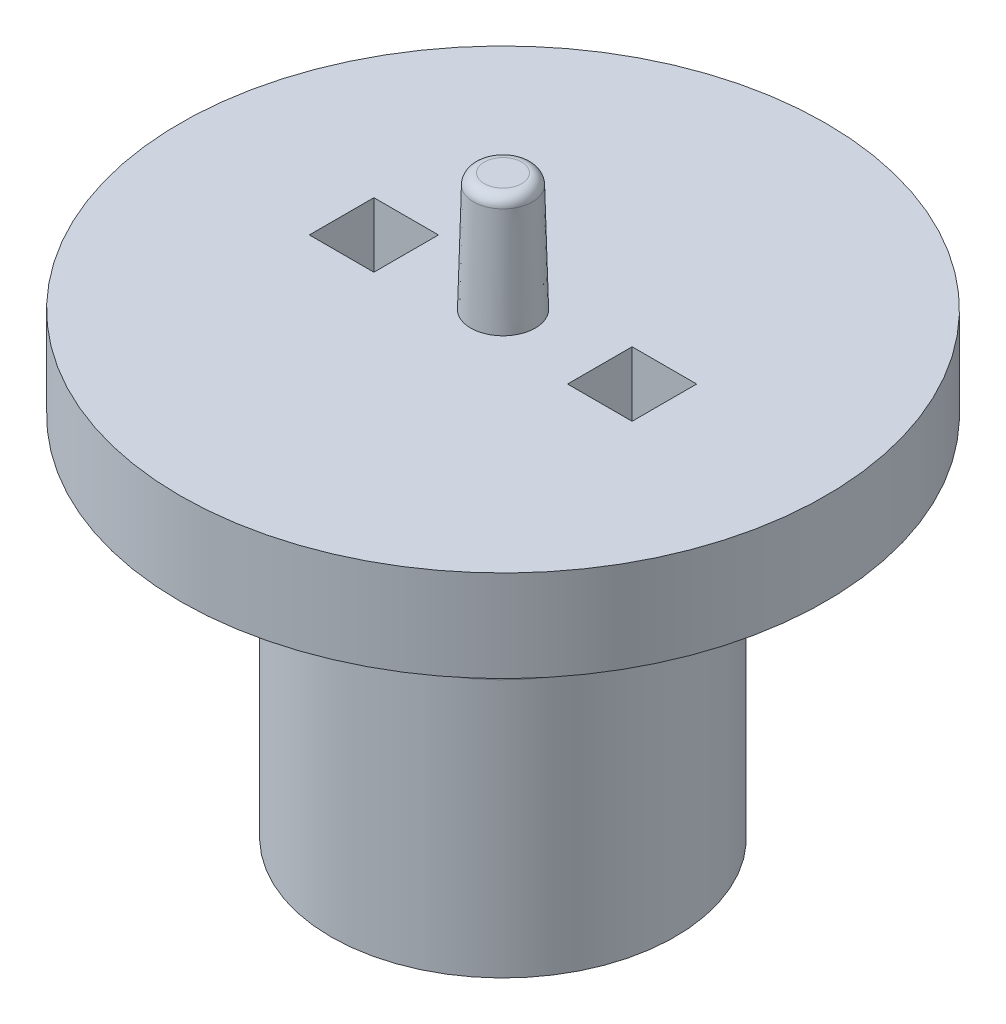
SolidWorks part; units mm, degrees
ref_plane "Front Plane" through (0, 0, 0) normal (0, 0, 1) x (1, 0, 0)
ref_plane "Top Plane" through (0, 0, 0) normal (0, 1, 0) x (1, 0, 0)
ref_plane "Right Plane" through (0, 0, 0) normal (1, 0, 0) x (0, 0, -1)
sketch "Sketch1" plane through (0, 0, 0) normal (0, 1, 0) x (1, 0, 0)
  circle A0 centre (0, 0) radius 8
  circle A1 centre (0, 0) radius 2.575
  dimension "D1" = 16
  dimension "D2" = 5.15
extrude "Boss-Extrude1" add sketch "Sketch1" along normal blind 15
sketch "Sketch2" plane through (0, 0, 0) normal (0, 0, 1) x (1, 0, 0)
  line L1 (0, 7.5) -> (0, 15) construction
  line L2 (0, 7.5) -> (0, 0) construction
  circle A0 centre (0, 7.5) radius 1.25
  dimension "D1" = 2.5
extrude "Cut-Extrude1" cut sketch "Sketch2" against normal through all contours A0
ref_plane "Plane1" through (0, 0, -8) normal (0, 0, -1) x (-1, 0, 0)
sketch "Sketch12" plane through (0, 15, 0) normal (0, 1, 0) x (1, 0, 0)
  circle A0 centre (0, 0) radius 8
  circle A1 centre (0, 0) radius 8 construction
extrude "Boss-Extrude3" add sketch "Sketch12" along normal blind 2
sketch "Sketch10" plane through (0, 17, 0) normal (0, 1, 0) x (1, 0, 0)
  circle A0 centre (0, 0) radius 7.5
sketch "Sketch11" plane through (0, 17, 0) normal (0, 1, 0) x (1, 0, 0)
  line L0 (6, 0) -> (0, 0) construction
  line L1 (-7.5, 1.5) -> (-4.5, 1.5)
  line L2 (-7.5, 1.5) -> (-7.5, -1.5)
  line L3 (-7.5, -1.5) -> (-4.5, -1.5)
  line L4 (-4.5, 1.5) -> (-4.5, -1.5)
  line L5 (-7.5, 1.5) -> (-4.5, -1.5) construction
  line L6 (-7.5, -1.5) -> (-4.5, 1.5) construction
  line L7 (4.5, 1.5) -> (7.5, 1.5)
  line L8 (4.5, 1.5) -> (4.5, -1.5)
  line L9 (4.5, -1.5) -> (7.5, -1.5)
  line L10 (7.5, 1.5) -> (7.5, -1.5)
  line L11 (4.5, 1.5) -> (7.5, -1.5) construction
  line L12 (4.5, -1.5) -> (7.5, 1.5) construction
  line L13 (0, 0) -> (-6, 0) construction
  circle A0 centre (0, 0) radius 15
  point P0 (-6, 0)
  point P5 (6, 0)
  dimension "D4" = 30
  dimension "D1" = 3
  dimension "D2" = 3
  dimension "D3" = 6
  dimension "D5" = 3
extrude "Boss-Extrude2" add sketch "Sketch11" along normal blind 4.25
sketch "Sketch13" plane through (0, 21.25, 0) normal (0, 1, 0) x (1, 0, 0)
  circle A0 centre (0, 0) radius 1.5
  dimension "D1" = 3
extrude "Boss-Extrude4" add sketch "Sketch13" along normal blind 5.5 draft 1.5
fillet "Fillet2" radius 0.5 1 edges at (0, 26.75, 1.356)
fillet "Fillet4" radius 5 1 edges at (0, 17, 8)
thread "Thread1" pitch 0.5 method cut profile "Thread Profile1" start angle 0, offset 11, length 10, pitch 0.5, diameter 2.5
ref_plane "Plane2" through (1.25, 7.5, -9.5) normal (0, -1, 0) x (1, 0, 0)
sketch "Thread Profile1" plane through (1.25, 7.5, -9.5) normal (0, -1, 0) x (1, 0, 0)
  line L0 (0, 0) -> (0, 0.5) construction
  line L1 (0, 0) -> (0.2706, 0.1562)
  line L2 (0.2706, 0.1562) -> (0.2706, 0.2187)
  line L3 (0.2706, 0.2187) -> (0, 0.375)
  line L4 (0.2706, 0.1875) -> (0, 0.1875) construction
  line L11 (0, 0) -> (0, 0.375)
  point P2 (0, 0)
  dimension "Pitch" = 0.5
  dimension "Profile_Angle" = 60
  dimension "Profile_Land" = 0.0625
  dimension "Profile_Height" = 0.2706
ref_plane "Plane4" through (0, 8.75, -8) normal (0, 0, -1) x (-1, 0, 0)
sketch "Sketch16" plane through (0, 8.75, -8) normal (0, 0, -1) x (-1, 0, 0)
  circle A0 centre (0, -1.25) radius 1.75
  arc A1 (0, 0) -> (-0.9513, -0.4392) centre (0, -1.25) ccw construction
  point P2 (0, 0)
  point P8 (0, 0)
  dimension "D1" = 3.5
extrude "Cut-Extrude2" cut sketch "Sketch16" against normal blind 10 draft 45
